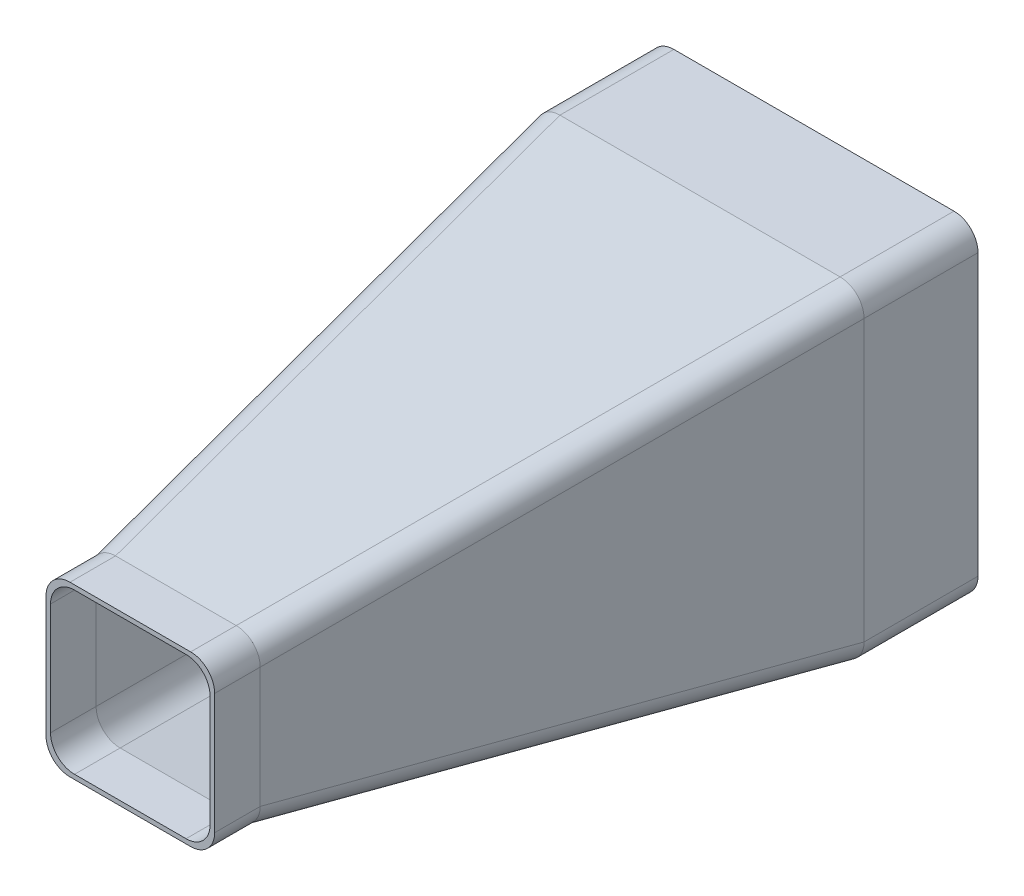
SolidWorks part; units mm, degrees
ref_plane "Front Plane" through (0, 0, 0) normal (0, 0, 1) x (1, 0, 0)
ref_plane "Top Plane" through (0, 0, 0) normal (0, 1, 0) x (1, 0, 0)
ref_plane "Right Plane" through (0, 0, 0) normal (1, 0, 0) x (0, 0, -1)
ref_plane "Plane1" through (0, 0, 130) normal (0, 0, 1) x (1, 0, 0)
ref_plane "Plane2" through (0, 0, -100) normal (0, 0, 1) x (1, 0, 0)
sketch "Sketch1" plane through (0, 0, 130) normal (0, 0, 1) x (1, 0, 0)
  line L1 (-37, -37) -> (37, -37)
  line L2 (-37, -37) -> (-37, 37)
  line L3 (-37, 37) -> (37, 37)
  line L4 (37, -37) -> (37, 37)
  line L5 (-37, -37) -> (37, 37) construction
  line L6 (-37, 37) -> (37, -37) construction
  line L7 (-35, -35) -> (35, -35)
  line L8 (-35, -35) -> (-35, 35)
  line L9 (-35, 35) -> (35, 35)
  line L10 (35, -35) -> (35, 35)
  line L11 (-35, -35) -> (35, 35) construction
  line L12 (-35, 35) -> (35, -35) construction
  point P0 (0, 0)
  point P6 (0, 0)
  dimension "D1" = 70
  dimension "D2" = 2
sketch "Sketch2" plane through (0, 0, -100) normal (0, 0, 1) x (1, 0, 0)
  line L0 (-37, -37) -> (37, 37) construction
  line L1 (-72, -72) -> (72, -72)
  line L2 (-72, -72) -> (-72, 72)
  line L3 (-72, 72) -> (72, 72)
  line L4 (72, -72) -> (72, 72)
  line L5 (-72, -72) -> (72, 72) construction
  line L6 (-72, 72) -> (72, -72) construction
  line L8 (-70, -70) -> (70, -70)
  line L9 (-70, -70) -> (-70, 70)
  line L10 (-70, 70) -> (70, 70)
  line L11 (70, -70) -> (70, 70)
  line L12 (-70, -70) -> (70, 70) construction
  line L13 (-70, 70) -> (70, -70) construction
  point P0 (0, 0)
  point P7 (0, 0)
  dimension "D1" = 140
  dimension "D2" = 2
loft "Loft1" add section "Sketch1" section "Sketch2" connector at (37, 37, 130) connector at (72, 72, -100)
loft "Cut-Loft1" cut section "Sketch1<29>" section "Sketch2<45>" connector at (35, 35, 130) connector at (70, 70, -100)
sketch "Sketch1<29>" plane through (0, 0, 130) normal (0, 0, 1) x (1, 0, 0) same geometry as "Sketch1"
sketch "Sketch2<45>" plane through (0, 0, -100) normal (0, 0, 1) x (1, 0, 0) same geometry as "Sketch2"
fillet "Fillet1" radius 10.65 8 edges
sketch "Sketch3" plane through (0, 0, -100) normal (0, 0, -1) x (-1, 0, 0)
  line L0 (59.4712, -70) -> (-59.4712, -70) construction
  line L1 (70, -59.4712) -> (70, 59.4712) construction
  line L2 (59.4712, 70) -> (-59.4712, 70) construction
  line L3 (-70, -59.4712) -> (-70, 59.4712) construction
  line L4 (-61.4712, -72) -> (61.4712, -72)
  line L5 (72, -61.4712) -> (72, 61.4712)
  line L6 (61.4712, 72) -> (-61.4712, 72)
  line L7 (-72, 61.4712) -> (-72, -61.4712)
  line L8 (-61.4712, -72) -> (61.4712, -72)
  line L9 (72, -61.4712) -> (72, 61.4712)
  line L10 (61.4712, 72) -> (-61.4712, 72)
  line L11 (-72, 61.4712) -> (-72, -61.4712)
  line L12 (59.4712, -70) -> (-59.4712, -70)
  line L13 (70, -59.4712) -> (70, 59.4712)
  line L14 (59.4712, 70) -> (-59.4712, 70)
  line L15 (-70, -59.4712) -> (-70, 59.4712)
  ellipse E0 centre (-59.2274, -59.2274) end of major axis (-51.5243, -51.5243) minor radius 10.65 (-70, -59.4712) -> (-59.4712, -70) ccw construction
  ellipse E1 centre (59.2274, -59.2274) end of major axis (66.9305, -66.9305) minor radius 10.65 (59.4712, -70) -> (70, -59.4712) ccw construction
  ellipse E2 centre (59.2274, 59.2274) end of major axis (51.5243, 51.5243) minor radius 10.65 (70, 59.4712) -> (59.4712, 70) ccw construction
  ellipse E3 centre (-59.2274, 59.2274) end of major axis (-66.9305, 66.9305) minor radius 10.65 (-59.4712, 70) -> (-70, 59.4712) ccw construction
  ellipse E4 centre (61.2274, -61.2274) end of major axis (53.5243, -53.5243) minor radius 10.65 (61.4712, -72) -> (72, -61.4712) ccw
  ellipse E5 centre (61.2274, 61.2274) end of major axis (53.5243, 53.5243) minor radius 10.65 (72, 61.4712) -> (61.4712, 72) ccw
  ellipse E6 centre (-61.2274, 61.2274) end of major axis (-53.5243, 53.5243) minor radius 10.65 (-61.4712, 72) -> (-72, 61.4712) ccw
  ellipse E7 centre (-61.2274, -61.2274) end of major axis (-53.5243, -53.5243) minor radius 10.65 (-72, -61.4712) -> (-61.4712, -72) ccw
  ellipse E8 centre (61.2274, -61.2274) end of major axis (53.5243, -53.5243) minor radius 10.65 (61.4712, -72) -> (72, -61.4712) ccw
  ellipse E9 centre (61.2274, 61.2274) end of major axis (68.9305, 68.9305) minor radius 10.65 (72, 61.4712) -> (61.4712, 72) ccw
  ellipse E10 centre (-61.2274, 61.2274) end of major axis (-68.9305, 68.9305) minor radius 10.65 (-61.4712, 72) -> (-72, 61.4712) ccw
  ellipse E11 centre (-61.2274, -61.2274) end of major axis (-68.9305, -68.9305) minor radius 10.65 (-72, -61.4712) -> (-61.4712, -72) ccw
  ellipse E12 centre (-59.2274, -59.2274) end of major axis (-51.5243, -51.5243) minor radius 10.65 (-70, -59.4712) -> (-59.4712, -70) ccw
  ellipse E13 centre (59.2274, -59.2274) end of major axis (66.9305, -66.9305) minor radius 10.65 (59.4712, -70) -> (70, -59.4712) ccw
  ellipse E14 centre (59.2274, 59.2274) end of major axis (66.9305, 66.9305) minor radius 10.65 (70, 59.4712) -> (59.4712, 70) ccw
  ellipse E15 centre (-59.2274, 59.2274) end of major axis (-66.9305, 66.9305) minor radius 10.65 (-59.4712, 70) -> (-70, 59.4712) ccw
  dimension "D1" = 0
extrude "Boss-Extrude1" add sketch "Sketch3" along normal blind 50
sketch "Sketch4" plane through (0, 0, 130) normal (0, 0, 1) x (1, 0, 0)
  line L0 (-24.4712, -35) -> (24.4712, -35) construction
  line L1 (35, -24.4712) -> (35, 24.4712) construction
  line L2 (-24.4712, 35) -> (24.4712, 35) construction
  line L3 (-35, -24.4712) -> (-35, 24.4712) construction
  line L4 (-37, 26.4712) -> (-37, -26.4712)
  line L5 (-26.4712, -37) -> (26.4712, -37)
  line L6 (37, -26.4712) -> (37, 26.4712)
  line L7 (26.4712, 37) -> (-26.4712, 37)
  line L8 (-37, 26.4712) -> (-37, -26.4712)
  line L9 (-26.4712, -37) -> (26.4712, -37)
  line L10 (37, -26.4712) -> (37, 26.4712)
  line L11 (26.4712, 37) -> (-26.4712, 37)
  line L12 (-24.4712, -35) -> (24.4712, -35)
  line L13 (35, -24.4712) -> (35, 24.4712)
  line L14 (-24.4712, 35) -> (24.4712, 35)
  line L15 (-35, -24.4712) -> (-35, 24.4712)
  ellipse E0 centre (-24.2274, -24.2274) end of major axis (-31.9305, -31.9305) minor radius 10.65 (-35, -24.4712) -> (-24.4712, -35) ccw construction
  ellipse E1 centre (24.2274, -24.2274) end of major axis (31.9305, -31.9305) minor radius 10.65 (24.4712, -35) -> (35, -24.4712) ccw construction
  ellipse E2 centre (24.2274, 24.2274) end of major axis (31.9305, 31.9305) minor radius 10.65 (35, 24.4712) -> (24.4712, 35) ccw construction
  ellipse E3 centre (-24.2274, 24.2274) end of major axis (-31.9305, 31.9305) minor radius 10.65 (-24.4712, 35) -> (-35, 24.4712) ccw construction
  ellipse E4 centre (-26.2274, -26.2274) end of major axis (-33.9305, -33.9305) minor radius 10.65 (-37, -26.4712) -> (-26.4712, -37) ccw
  ellipse E5 centre (26.2274, -26.2274) end of major axis (33.9305, -33.9305) minor radius 10.65 (26.4712, -37) -> (37, -26.4712) ccw
  ellipse E6 centre (26.2274, 26.2274) end of major axis (18.5243, 18.5243) minor radius 10.65 (37, 26.4712) -> (26.4712, 37) ccw
  ellipse E7 centre (-26.2274, 26.2274) end of major axis (-33.9305, 33.9305) minor radius 10.65 (-26.4712, 37) -> (-37, 26.4712) ccw
  ellipse E8 centre (-26.2274, -26.2274) end of major axis (-33.9305, -33.9305) minor radius 10.65 (-37, -26.4712) -> (-26.4712, -37) ccw
  ellipse E9 centre (26.2274, -26.2274) end of major axis (33.9305, -33.9305) minor radius 10.65 (26.4712, -37) -> (37, -26.4712) ccw
  ellipse E10 centre (26.2274, 26.2274) end of major axis (18.5243, 18.5243) minor radius 10.65 (37, 26.4712) -> (26.4712, 37) ccw
  ellipse E11 centre (-26.2274, 26.2274) end of major axis (-33.9305, 33.9305) minor radius 10.65 (-26.4712, 37) -> (-37, 26.4712) ccw
  ellipse E12 centre (-24.2274, -24.2274) end of major axis (-31.9305, -31.9305) minor radius 10.65 (-35, -24.4712) -> (-24.4712, -35) ccw
  ellipse E13 centre (24.2274, -24.2274) end of major axis (16.5243, -16.5243) minor radius 10.65 (24.4712, -35) -> (35, -24.4712) ccw
  ellipse E14 centre (24.2274, 24.2274) end of major axis (31.9305, 31.9305) minor radius 10.65 (35, 24.4712) -> (24.4712, 35) ccw
  ellipse E15 centre (-24.2274, 24.2274) end of major axis (-31.9305, 31.9305) minor radius 10.65 (-24.4712, 35) -> (-35, 24.4712) ccw
  dimension "D1" = 0
extrude "Boss-Extrude2" add sketch "Sketch4" along normal blind 20
sketch "Sketch5" plane through (0, -55.4975, 8.4453) normal (0, -0.9886, 0.1504) x (1, 0, 0)
  line L0 (0, 89.6937) -> (0, -89.6937) construction
  line L1 (-61.4712, -109.6937) -> (61.4712, -109.6937) construction
  circle A0 centre (0, 89.6937) radius 2.5
  circle A1 centre (0, 0) radius 2.5
  circle A2 centre (0, -89.6937) radius 2.5
  dimension "D1" = 5
  dimension "D2" = 20
extrude "Cut-Extrude1" cut sketch "Sketch5" against normal up to next
